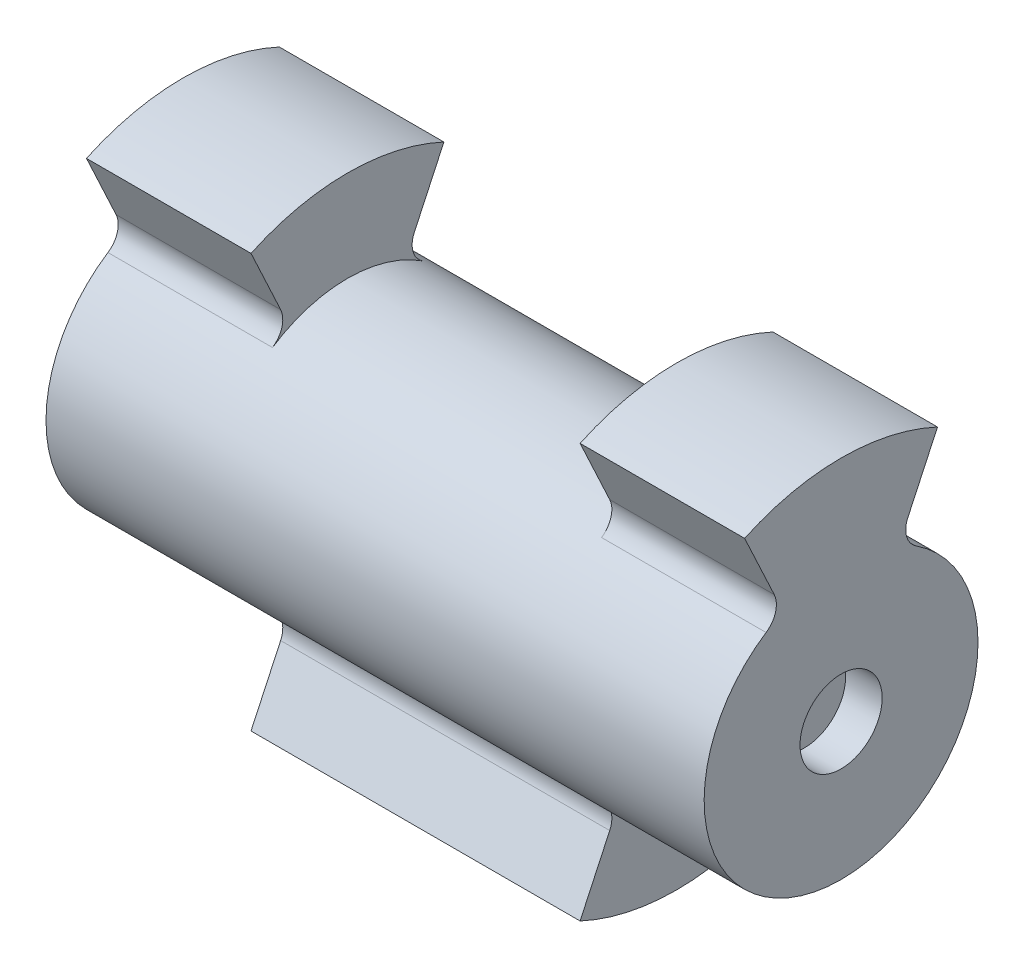
SolidWorks part; units mm, degrees
ref_plane "Front Plane" through (0, 0, 0) normal (0, 0, 1) x (1, 0, 0)
ref_plane "Top Plane" through (0, 0, 0) normal (0, 1, 0) x (1, 0, 0)
ref_plane "Right Plane" through (0, 0, 0) normal (1, 0, 0) x (0, 0, -1)
sketch "Sketch1" plane through (0, 0, 0) normal (1, 0, 0) x (0, 0, -1)
  circle A0 centre (0, 0) radius 30
extrude "Boss-Extrude1" add sketch "Sketch1" along normal blind 72.1 and the other way blind 72.1
sketch "Sketch3" plane through (72.1, 0, 0) normal (1, 0, 0) x (0, 0, -1)
  line L0 (0, 0) -> (0, 50) construction
  line L3 (7.6071, 16.3135) -> (21.1309, 45.3154)
  line L4 (-7.6071, 16.3135) -> (-21.1309, 45.3154)
  arc A0 (21.1309, 45.3154) -> (-21.1309, 45.3154) centre (0, 0) ccw
  arc A1 (7.6071, 16.3135) -> (-7.6071, 16.3135) centre (0, 0) ccw
  dimension "D1" = 25
  dimension "D2" = 50
extrude "Boss-Extrude2" add sketch "Sketch3" against normal blind 36.05
mirror "Mirror1" about plane through (0, 0, 0) normal (1, 0, 0) of bodies 102
sketch "Sketch4" plane through (0, 0, 0) normal (1, 0, 0) x (0, 0, -1)
  line L0 (0, -18) -> (0, -50) construction
  line L1 (-7.6071, -16.3135) -> (-21.1309, -45.3154)
  line L2 (7.6071, -16.3135) -> (21.1309, -45.3154)
  line L3 (0, 0) -> (0, -50) construction
  arc A0 (-21.1309, -45.3154) -> (21.1309, -45.3154) centre (0, 0) ccw
  arc A1 (-7.6071, -16.3135) -> (7.6071, -16.3135) centre (0, 0) ccw
  dimension "D1" = 25
  dimension "D2" = 50
extrude "Boss-Extrude3" add sketch "Sketch4" along normal blind 36.05 and the other way blind 36.05
sketch "Sketch5" plane through (72.1, 0, 0) normal (1, 0, 0) x (0, 0, -1)
  circle A0 centre (0, 0) radius 9
extrude "Cut-Extrude1" cut sketch "Sketch5" against normal blind 8
mirror "Mirror3" about plane through (0, 0, 0) normal (1, 0, 0) of "Cut-Extrude1"
fillet "Fillet1" radius 5 6 edges at (0, -27.1892, 12.6785) (0, -27.1892, -12.6785) (54.075, 27.1892, -12.6785) (54.075, 27.1892, 12.6785) (-54.075, 27.1892, -12.6785) (-54.075, 27.1892, 12.6785)
